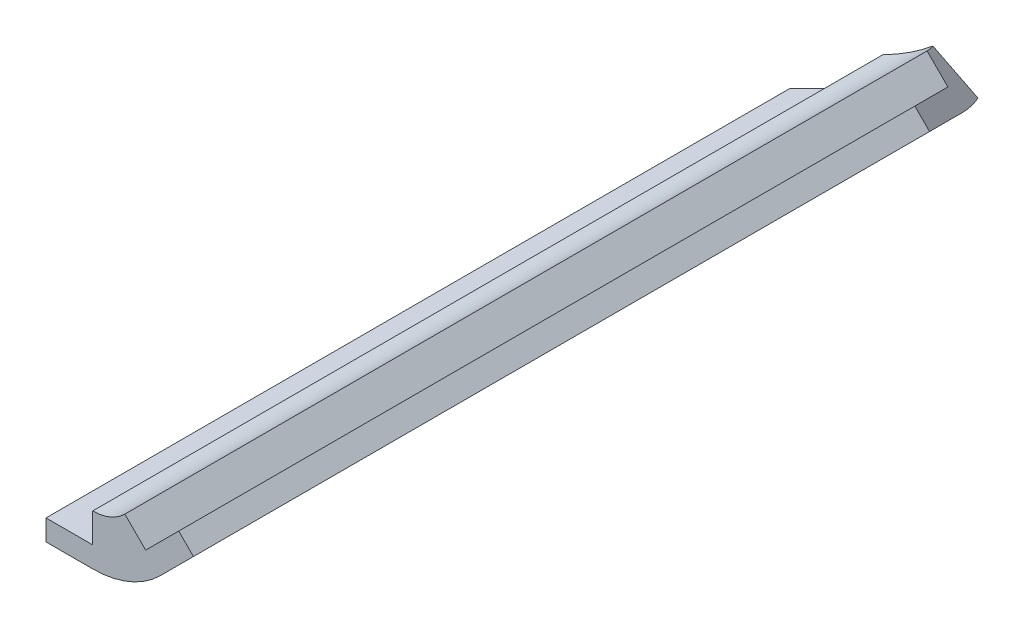
SolidWorks part; units mm, degrees
note: '?' marks a value the reader was unsure of.
ref_plane "Front Plane" through (0, 0, 0) normal (0, 0, 1) x (1, 0, 0)
ref_plane "Top Plane" through (0, 0, 0) normal (0, 1, 0) x (1, 0, 0)
ref_plane "Right Plane" through (0, 0, 0) normal (1, 0, 0) x (0, 0, -1)
ref_axis "Axis1" through (0, 0, -88.99) along (0, 0, 1)?
sketch "Sketch16" plane through (0, 0, 0) normal (0, 1, 0) x (1, 0, 0)
  line L0 (0, -127) -> (0, 127) construction
  point P2 (0, 0)
  dimension "D1" = 254
sketch "Sketch2" plane through (0, 0, 0) normal (0, 0, 1) x (1, 0, 0)
  line L0 (-7.3025, -1.5) -> (-2.54, -1.5) construction
  line L1 (-7.3025, -1.5) -> (-7.3025, 1.5) construction
  line L2 (-2.54, -1.5) -> (-2.54, 1.5) construction
  line L3 (-7.3025, 1.5) -> (-2.54, 1.5) construction
  line L4 (-2.54, 0) -> (0, 0) construction
  line L5 (0, 0) -> (1.7961, 1.7961) construction
  line L6 (2.8567, 0.7354) -> (0.7354, 2.8567) construction
  line L7 (2.8567, 0.7354) -> (6.2243, 4.103) construction
  line L8 (0.7354, 2.8567) -> (4.103, 6.2243) construction
  line L9 (6.2243, 4.103) -> (4.103, 6.2243) construction
  point P7 (1.7961, 1.7961)
  point P16 (-0.6213, 1.5)
  dimension "D1" = 3
  dimension "D2" = 4.7625
  dimension "D3" = 2.54
  dimension "D4" = 135
ref_plane "Plane1" through (0, 0, 0) normal (-0.7071, 0.7071, 0) x (0.7071, 0.7071, 0)
sketch "Sketch7" plane through (0, 0, 0) normal (0, 0, 1) x (1, 0, 0)
  line L0 (-7.3025, -1.5) -> (-2.54, -1.5)
  line L1 (-7.3025, -1.5) -> (-7.3025, -3.6212)
  line L2 (-2.54, -1.5) -> (-2.54, -3.6212)
  line L3 (-7.3025, -3.6212) -> (-2.54, -3.6212)
  dimension "D1" = 2.1212
extrude "Boss-Extrude2" add sketch "Sketch7" along normal mid plane 260.35 separate body
sketch "Sketch8" plane through (0, 0, 0) normal (0, 0, 1) x (1, 0, 0)
  line L0 (2.8567, 0.7354) -> (6.2243, 4.103)
  line L1 (2.8567, 0.7354) -> (4.3566, -0.7645)
  line L2 (6.2243, 4.103) -> (7.7242, 2.6031)
  line L3 (4.3566, -0.7645) -> (7.7242, 2.6031)
  line L4 (-2.54, -3.6212) -> (-2.54, -1.5) construction
extrude "Boss-Extrude3" add sketch "Sketch8" along normal mid plane 260.35
sketch "Sketch11" plane through (0, 0, 0) normal (0, 0, 1) x (1, 0, 0)
  line L1 (-2.54, -1.5) -> (-7.3025, -1.5)
  line L2 (-7.3025, -1.5) -> (-7.3025, -3.6212)
  line L8 (7.7242, 2.6031) -> (6.2243, 4.103)
  line L9 (6.2243, 4.103) -> (2.8567, 0.7354)
  line L13 (2.8567, 0.7354) -> (0.7354, 2.8567)
  line L14 (0.7354, 2.8567) -> (-0.6213, 1.5) construction
  line L15 (-0.6213, 1.5) -> (-2.54, 1.5) construction
  line L17 (-2.54, 1.5) -> (-2.54, -1.5)
  line L18 (7.7242, 2.6031) -> (4.3566, -0.7645)
  line L19 (2.8567, 0.7354) -> (4.3566, -0.7645) construction
  line L20 (-2.54, -3.6212) -> (-7.3025, -3.6212)
  arc A0 (0.7354, 2.8567) -> (-2.54, 1.5) centre (-2.54, 6.1321) cw
  arc A1 (4.3566, -0.7645) -> (-2.54, -3.6212) centre (-2.54, 6.1321) cw
extrude "Boss-Extrude4" add sketch "Sketch11" along normal mid plane 260.35
ref_plane "Midplane" through (0, 0, 0) normal (0.9239, 0.3827, 0) x (0.3827, -0.9239, 0)
sketch "Sketch17" plane through (47.0981, -113.7049, 0) normal (0, -1, 0) x (-1, 0, 0)
  line L0 (-898.0256, 898.0256) -> (898.0256, -898.0256)
  line L1 (-898.0256, 898.0256) -> (898.0256, 2694.0768)
  line L2 (898.0256, -898.0256) -> (2694.0768, 898.0256)
  line L3 (898.0256, 2694.0768) -> (2694.0768, 898.0256)
  line L4 (36.4768, 0) -> (203.8208, 0) construction
  point P0 (157.3744, -157.3744)
  point P8 (0, 0)
  dimension "D1" = 45
  dimension "D2" = 2540
extrude "Cut-Extrude1" cut sketch "Sketch17" against normal through all both and the other way through all
sketch "Sketch18" plane through (47.0981, 47.0981, 0) normal (0.5774, 0.5774, -0.5774) x (0.8165, -0.4082, 0.4082)
  line L1 (-127, -127) -> (127, -127)
  line L2 (-127, -127) -> (-127, 127)
  line L3 (-127, 127) -> (127, 127)
  line L4 (127, -127) -> (127, 127)
  line L5 (-127, -127) -> (127, 127) construction
  line L6 (-127, 127) -> (127, -127) construction
  point P0 (0, 0)
  dimension "D1" = 254
extrude "Cut-Extrude2" cut sketch "Sketch18" against normal up to vertex (80.2615 mm away)
equation "\"plate_thickness\"= 3mm"
equation "\"D1@Sketch2\"=\"plate_thickness\""
equation "\"joiner_lip_width\"= .1875"
equation "\"D2@Sketch2\"=\"joiner_lip_width\""
equation "\"face_gap\"=0.1"
equation "\"D3@Sketch2\"=\"face_gap\""
equation "\"inside_angle\"= 135deg"
equation "\"joiner_thickness\"= 0.0835128"
equation "\"edge_length\"= 10"
equation "\"Face1_TopLip\"= \"angle\" * 2"
equation "\"Face1_BottomLip\"= \"angle\" * 2"
equation "\"Face2_TopLip\"= 45deg"
equation "\"Face2_BottomLip\"= 45deg"
equation "\"D1@Sketch7\"=\"joiner_thickness\""
equation "\"D1@Boss-Extrude2\"=\"Extrude_to\""
equation "\"D1@Boss-Extrude3\"=\"Extrude_to\""
equation "\"D1@Boss-Extrude4\"=\"Extrude_to\""
equation "\"Extrude_to\"= \"edge_length\" + .25"
equation "\"D1@Sketch16\"=\"edge_length\""
equation "\"angle\"= atn ( 0.1 / ( ( 3.7085 - 3.0793 ) / 2 ) )"
equation "\"D4@Sketch2\"=\"inside_angle\""
equation "\"D2@Sketch5\"=\"Face2_TopLip\"/2"
equation "\"D1@Sketch5\"=\"Face2_BottomLip\"/2"
equation "\"D2@Sketch4\"=\"Face1_TopLip\"/2"
equation "\"D1@Sketch4\"=\"Face1_BottomLip\"/2"
equation "\"D1\" = \"edge_length\""
equation "\"D2@Sketch12\"=\"Face1_TopLip\"/2"
equation "\"D1@Sketch12\"=\"Face1_BottomLip\"/2"
